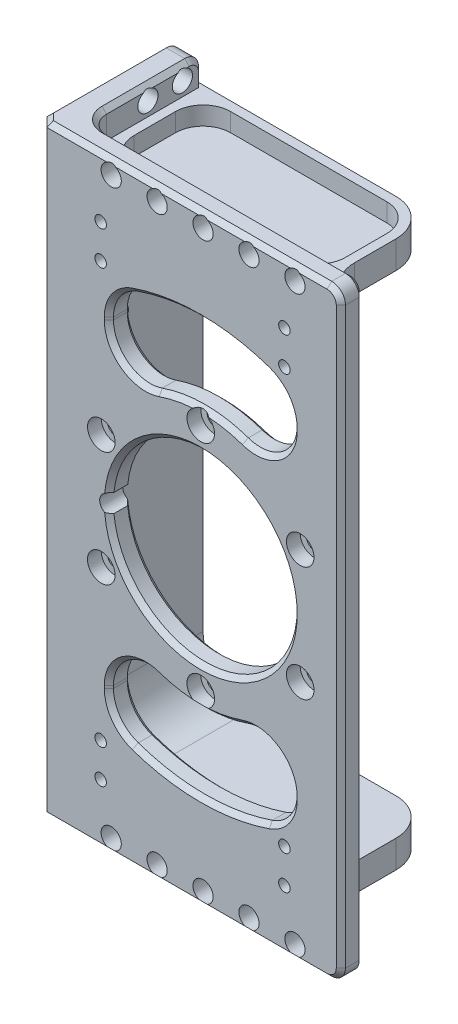
SolidWorks part; units mm, degrees
material "6061 合金"
ref_plane "前视基准面" through (0, 0, 0) normal (0, 0, 1) x (1, 0, 0)
ref_plane "上视基准面" through (0, 0, 0) normal (0, 1, 0) x (1, 0, 0)
ref_plane "右视基准面" through (0, 0, 0) normal (1, 0, 0) x (0, 0, -1)
sketch "草图1" plane through (0, 0, 0) normal (0, 0, 1) x (1, 0, 0)
  line L0 (-237.1759, 120) -> (-237.1759, 1) construction
  line L1 (-237.1759, 60.5) -> (-177.1759, 60.5) construction
  line L2 (812.8241, 60.5) -> (-387.1759, 60.5) construction
  line L3 (-165.4601, -5) -> (-232.1759, -5) construction
  line L4 (-237.1759, 126) -> (-177.1759, 126)
  line L5 (-237.1759, 126) -> (-237.1759, -5)
  line L6 (-237.1759, -5) -> (-177.1759, -5)
  line L7 (-177.1759, 126) -> (-177.1759, -5)
extrude "凸台-拉伸1" add sketch "草图1" along normal blind 5
sketch "草图2" plane through (-237.1759, 0, 0) normal (-1, 0, 0) x (0, 0, 1)
  line L0 (-235, 126) -> (-5, 126) construction
  line L1 (5, -5) -> (-25, -5)
  line L2 (5, -5) -> (5, 126)
  line L3 (5, 126) -> (-25, 126)
  line L4 (-25, -5) -> (-25, 126)
extrude "凸台-拉伸2" add sketch "草图2" along normal blind 6
sketch "草图3" plane through (0, 0, 5) normal (0, 0, 1) x (1, 0, 0)
  line L2 (-236.1759, 60.5) -> (-179.1759, 60.5) construction
  circle A2 centre (-207.6759, 60.5) radius 28.5 construction
  circle A3 centre (-207.6759, 60.5) radius 25 construction
  circle A4 centre (-207.6759, 60.5) radius 20
  dimension "D1" = 5
extrude "切除-拉伸1" cut sketch "草图3" against normal blind 10
sketch "草图4" plane through (0, 0, 5) normal (0, 0, 1) x (1, 0, 0)
  line L4 (-177.1759, 126) -> (-243.1759, 126)
  line L5 (-243.1759, 126) -> (-243.1759, -5)
  line L6 (-243.1759, -5) -> (-177.1759, -5)
  line L7 (-177.1759, -5) -> (-177.1759, 126)
  line L8 (-177.1759, 126) -> (-243.1759, 126)
  line L9 (-243.1759, 126) -> (-243.1759, -5)
  line L10 (-243.1759, -5) -> (-177.1759, -5)
  line L11 (-177.1759, -5) -> (-177.1759, 126)
  circle A0 centre (-207.6759, 60.5) radius 20 construction
  circle A1 centre (-207.6759, 60.5) radius 20
  dimension "D1" = 0
chamfer "倒角1" distance 2 angle 45 1 edges at (-243.1759, 60.5, 5)
fillet "圆角1" radius 3 4 edges at (-240.1759, 126, -25) (-177.1759, 126, 2.5) (-177.1759, -5, 2.5) (-240.1759, -5, -25)
sketch "草图5" plane through (0, 0, 5) normal (0, 0, 1) x (1, 0, 0)
  circle A0 centre (-207.6759, 60.5) radius 25 construction
  point P3 (-207.6759, 85.5)
  point P4 (-186.0252, 73)
  point P7 (-186.0252, 48)
  point P8 (-207.6759, 35.5)
  point P9 (-229.3265, 48)
  point P10 (-229.3265, 73)
  point P11 (-207.6759, 60.5)
  dimension "D1" = 6
sketch "草图13" plane through (0, 0, 5) normal (0, 0, 1) x (1, 0, 0)
  circle A0 centre (-207.6759, 85.5) radius 1.6
  circle A1 centre (-229.3265, 73) radius 1.6
  circle A2 centre (-186.0252, 73) radius 1.6
  circle A3 centre (-186.0252, 48) radius 1.6
  circle A4 centre (-207.6759, 35.5) radius 1.6
  circle A5 centre (-229.3265, 48) radius 1.6
extrude "切除-拉伸2" cut sketch "草图13" against normal blind 6
sketch "草图14" plane through (0, 0, 5) normal (0, 0, 1) x (1, 0, 0)
  circle A0 centre (-207.6759, 85.5) radius 3
  circle A1 centre (-186.0252, 73) radius 3
  circle A2 centre (-186.0252, 48) radius 3
  circle A3 centre (-207.6759, 35.5) radius 3
  circle A4 centre (-229.3265, 48) radius 3
  circle A5 centre (-229.3265, 73) radius 3
extrude "切除-拉伸3" cut sketch "草图14" against normal blind 3
chamfer "倒角4" distance 1 angle 45 12 edges at (-242.1759, -5, 4) (-210.6759, -5, 5) (-243.1759, -5, -9.5) (-178.0545, -4.1213, 5) (-243.1759, -4.1213, -24.1213) (-177.1759, 60.5, 5) (-243.1759, 60.5, -25) (-178.0545, 125.1213, 5) (-243.1759, 125.1213, -24.1213) (-210.6759, 126, 5) (-242.1759, 126, 4) (-243.1759, 126, -9.5)
sketch "草图15" plane through (0, 0, 0) normal (0, -1, 0) x (1, 0, 0)
  line L0 (-11.5, -120) -> (-5.5, -120) construction
  line L1 (-11.5, -191) -> (-11.5, -49) construction
  line L2 (-5.5, -108) -> (-5.5, -132) construction
  line L3 (-8.5, -100) -> (-8.5, -140) construction
  line L4 (-8.5, -80) -> (-8.5, -160) construction
  line L5 (-8.5, -60) -> (-8.5, -180) construction
  point P9 (-8.5, -120)
  point P13 (-8.5, -120)
  point P16 (-8.5, -120)
sketch "草图16" plane through (0, 0, 0) normal (0, 0, -1) x (-1, 0, 0)
  line L5 (237.1759, 126) -> (237.1759, 120) construction
  line L6 (237.1759, 123) -> (237.1759, -2) construction
  line L8 (237.1759, 120) -> (187.1759, 120)
  line L9 (237.1759, 120) -> (237.1759, 114)
  line L10 (237.1759, 114) -> (187.1759, 114)
  line L11 (187.1759, 120) -> (187.1759, 114)
extrude "凸台-拉伸4" add sketch "草图16" along normal up to surface (25 mm away) up to face at (-239.6759, 60.5, -25)
ref_plane "基准面1" through (0, 60.5, 0) normal (0, -1, 0) x (-1, 0, 0)
mirror "镜向1" about plane through (0, 60.5, 0) normal (0, -1, 0) of "凸台-拉伸4"
fillet "圆角3" radius 4 2 edges at (-237.1759, -2, 0) (-237.1759, 123, 0)
fillet "圆角4" radius 10 2 edges at (-237.1759, 114, -12.5) (-237.1759, 7, -12.5)
fillet "圆角5" radius 8 4 edges at (-187.1759, 117, 0) (-187.1759, 117, -25) (-187.1759, 4, 0) (-187.1759, 4, -25)
sketch "草图17" plane through (0, 120, 0) normal (0, 1, 0) x (1, 0, 0)
  line L4 (-235.1759, 4) -> (-235.1759, 2)
  line L5 (-235.1759, 2) -> (-233.1759, 2)
  line L8 (-189.1759, 8) -> (-189.1759, 17)
  line L9 (-195.1759, 23) -> (-235.1759, 23)
  line L10 (-235.1759, 23) -> (-235.1759, 4)
  line L11 (-233.1759, 2) -> (-187.1759, 2)
  line L12 (-189.1759, 8) -> (-189.1759, 17)
  line L13 (-195.1759, 23) -> (-235.1759, 23)
  line L14 (-235.1759, 23) -> (-235.1759, 4)
  line L15 (-233.1759, 2) -> (-187.1759, 2)
  arc A6 (-189.1759, 17) -> (-195.1759, 23) centre (-195.1759, 17) ccw
  arc A7 (-235.1759, 4) -> (-233.1759, 2) centre (-233.1759, 4) ccw
  arc A8 (-189.1759, 8) -> (-187.1759, 2) centre (-179.1759, 8) ccw
  arc A9 (-189.1759, 17) -> (-195.1759, 23) centre (-195.1759, 17) ccw
  arc A11 (-189.1759, 8) -> (-187.1759, 2) centre (-179.1759, 8) ccw
  dimension "D1" = 2
extrude "切除-拉伸4" cut sketch "草图17" against normal blind 4
mirror "镜向2" about plane through (0, 60.5, 0) normal (0, -1, 0) of "切除-拉伸4"
fillet "圆角6" radius 6 6 edges at (-187.1759, 118, -2) (-235.1759, 118, -23) (-235.1759, 118, -2) (-235.1759, 3, -23) (-187.1759, 3, -2) (-235.1759, 3, -2)
sketch "草图19" plane through (0, 0, 5) normal (0, 0, 1) x (1, 0, 0)
  line L0 (-243.1759, -5) -> (-237.1759, -5) construction
  line L1 (-243.1759, -5) -> (-177.1759, -5) construction
  line L2 (-237.1759, -5) -> (-177.1759, -5) construction
  line L3 (-207.1759, -5) -> (-207.1759, 1) construction
  line L4 (-217.1759, -2) -> (-197.1759, -2)
  line L5 (-227.1759, -2) -> (-187.1759, -2)
  circle A0 centre (-227.1759, -2) radius 2.2
  circle A1 centre (-217.1759, -2) radius 2.2
  circle A2 centre (-207.1759, -2) radius 2.2
  circle A3 centre (-197.1759, -2) radius 2.2
  circle A4 centre (-187.1759, -2) radius 2.2
  point P13 (-207.1759, -2)
  point P15 (-207.1759, -2)
  line M14 (-241.1759, -4) -> (-180.1759, -4)
extrude "切除-拉伸5" cut sketch "草图19" against normal blind 18 contours A0 M14 | L4 A1 L5 | L4 A2 | L5 A3 L4 | A4 M14 | L4 A3 L5 M14 | L4 A2 M14 | L5 A1 L4 M14 | A4 M14 | A3 M14 | A2 M14 | A1 M14 | A0 M14 region at (-217.1759, -1.0663, 5) region at (-217.1759, -2.8953, 5) region at (-207.1759, -1.0663, 5) region at (-207.1759, -2.8953, 5) region at (-217.1759, -4.0803, 5) region at (-227.1759, -1.9657, 5) region at (-207.1759, -4.0803, 5) region at (-227.1759, -4.0803, 5) region at (-197.1759, -1.0663, 5) region at (-197.1759, -2.8953, 5) region at (-197.1759, -4.0803, 5) region at (-187.1759, -1.9657, 5) region at (-187.1759, -4.0803, 5)
mirror "镜向3" about plane through (0, 60.5, 0) normal (0, -1, 0) of "切除-拉伸5"
sketch "草图20" plane through (-243.1759, 0, 0) normal (-1, 0, 0) x (0, 0, 1)
  line L0 (5, -5) -> (-1, -5) construction
  line L1 (5, -5) -> (5, 126) construction
  line L2 (4, -5) -> (2.5858, -5) construction
  line L3 (-1, -5) -> (-25, -5) construction
  line L4 (-5, -5) -> (-235, -5) construction
  line L5 (-13, -5) -> (-13, 1) construction
  line L6 (-20.5, -2) -> (-5.5, -2) construction
  circle A0 centre (-20.5, -2) radius 2.2
  circle A1 centre (-13, -2) radius 2.2
  point P15 (-13, -2)
extrude "切除-拉伸6" cut sketch "草图20" against normal blind 18
mirror "镜向4" about plane through (0, 60.5, 0) normal (0, -1, 0) of "切除-拉伸6"
sketch "草图21" plane through (0, 0, 5) normal (0, 0, 1) x (1, 0, 0)
  line L0 (-207.6759, 60.5) -> (-209.4659, 60.5)
  line L1 (-14.3, 60.5) -> (14.3, 60.5) construction
  line L2 (-209.4659, 60.5) -> (-209.4659, 64.19)
  line L4 (-229.4659, 113.065) -> (-189.4659, 113.065)
  line L5 (-229.4659, 113.065) -> (-229.4659, 15.315)
  line L6 (-229.4659, 15.315) -> (-189.4659, 15.315)
  line L7 (-189.4659, 113.065) -> (-189.4659, 15.315)
  line L8 (-229.4659, 113.065) -> (-189.4659, 15.315) construction
  line L9 (-229.4659, 15.315) -> (-189.4659, 113.065) construction
hole_wizard "M3 螺纹孔1" positions "草图22" profile "草图23" tap size "M3" standard "GB"
sketch "草图22" plane through (0, 0, 5) normal (0, 0, 1) x (1, 0, 0)
  point P0 (-229.4659, 113.065)
  point P3 (-189.4659, 113.065)
  point P6 (-189.4659, 15.315)
  point P9 (-229.4659, 15.315)
sketch "草图23" plane through (-229.4659, 113.065, 5) normal (1, 0, 0) x (0, -1, 0)
  line L0 (0, 0) -> (0, 8.2511)
  line L1 (0, 8.2511) -> (1.25, 7.5)
  line L2 (1.25, 7.5) -> (1.25, 0)
  line L5 (1.25, 0) -> (0, 0)
  line L10 (0, 8.2511) -> (-1.25, 7.5) construction
  line L11 (0, -6.35) -> (0, 107.95) construction
  dimension "螺纹孔钻头直径" = 2.5
  dimension "螺纹孔钻头深度" = 7.5
  dimension "导头角度" = 118
cosmetic thread "孔螺蚊线1" parameters "D1"=6, "D2"=3
cosmetic thread "孔螺蚊线2" parameters "D1"=6, "D2"=3
cosmetic thread "孔螺蚊线3" parameters "D1"=6, "D2"=3
cosmetic thread "孔螺蚊线4" parameters "D1"=6, "D2"=3
mirror "镜向5" about plane through (0, 60.5, 0) normal (0, -1, 0) of "M3 螺纹孔1"
cosmetic thread "孔螺蚊线5" parameters "D1"=6, "D2"=3
cosmetic thread "孔螺蚊线6" parameters "D1"=6, "D2"=3
cosmetic thread "孔螺蚊线7" parameters "D1"=6, "D2"=3
cosmetic thread "孔螺蚊线8" parameters "D1"=6, "D2"=3
sketch "草图24" plane through (-243.1759, 0, 0) normal (-1, 0, 0) x (0, 0, 1)
  line L0 (5, 60.5) -> (-7.12, 60.5)
  line L3 (-14.3, 60.5) -> (14.3, 60.5) construction
  line L4 (-7.12, 60.5) -> (-7.12, 35.2)
  line L5 (-7.12, 60.5) -> (-7.12, 85.8)
hole_wizard "M4 螺纹孔1" positions "草图25" profile "草图26" tap size "M4" standard "GB"
sketch "草图25" plane through (-243.1759, 0, 0) normal (-1, 0, 0) x (0, 0, 1)
  point P0 (-7.12, 85.8)
  point P3 (-7.12, 35.2)
sketch "草图26" plane through (-243.1759, 85.8, -7.12) normal (0, 1, 0) x (0, 0, 1)
  line L0 (0, 0) -> (0, 11.0914)
  line L1 (0, 11.0914) -> (1.65, 10.1)
  line L2 (1.65, 10.1) -> (1.65, 0)
  line L5 (1.65, 0) -> (0, 0)
  line L10 (0, 11.0914) -> (-1.65, 10.1) construction
  line L11 (0, -6.35) -> (0, 107.95) construction
  dimension "螺纹孔钻头直径" = 3.3
  dimension "螺纹孔钻头深度" = 10.1
  dimension "导头角度" = 118
cosmetic thread "孔螺蚊线9" parameters "D1"=8, "D2"=4
cosmetic thread "孔螺蚊线10" parameters "D1"=8, "D2"=4
sketch "草图27" plane through (0, 0, 0) normal (0, 0, -1) x (-1, 0, 0)
  line L0 (207.6759, 105.5) -> (207.6759, 89) construction
  line L1 (187.6759, 100.8113) -> (187.6759, 80.8039)
  line L2 (227.6759, 100.8113) -> (227.6759, 80.8039)
  line L3 (227.6759, 60.5) -> (227.6759, -966.5522) construction
  line L4 (207.6759, 60.5) -> (207.6759, -966.5522) construction
  line L5 (187.6759, 60.5) -> (187.6759, -966.5522) construction
  line L6 (187.6759, 40.1961) -> (187.6759, 20.1887)
  line L7 (207.6759, 32) -> (207.6759, 15.5) construction
  line L8 (227.6759, 40.1961) -> (227.6759, 20.1887)
  arc A0 (187.6759, 40.1961) -> (227.6759, 40.1961) centre (207.6759, 60.5) ccw
  arc A1 (187.6759, 20.1887) -> (227.6759, 20.1887) centre (207.6759, 60.5) ccw
  arc A2 (227.6759, 80.8039) -> (187.6759, 80.8039) centre (207.6759, 60.5) ccw
  arc A3 (227.6759, 100.8113) -> (187.6759, 100.8113) centre (207.6759, 60.5) ccw
  dimension "D1" = 20
  dimension "D2" = 20
extrude "切除-拉伸7" cut sketch "草图27" against normal blind 10
fillet "圆角7" radius 8 8 edges at (-187.6759, 20.1887, 2.5) (-227.6759, 40.1961, 2.5) (-227.6759, 20.1887, 2.5) (-187.6759, 40.1961, 2.5) (-187.6759, 80.8039, 2.5) (-227.6759, 100.8113, 2.5) (-227.6759, 80.8039, 2.5) (-187.6759, 100.8113, 2.5)
chamfer "倒角5" distance 1 angle 45 34 edges at (-187.6759, 60.5, 0) (-187.6759, 60.5, 5) (-207.6759, 105.5, 0) (-189.166, 100.1499, 0) (-226.1857, 100.1499, 0) (-187.6759, 95.2355, 0) (-227.6759, 95.2355, 0) (-191.0413, 88.4502, 0) (-224.3105, 88.4502, 0) (-207.6759, 89, 0) (-207.6759, 89, 5) (-191.0413, 88.4502, 5) (-224.3105, 88.4502, 5) (-187.6759, 95.2355, 5) (-227.6759, 95.2355, 5) (-189.166, 100.1499, 5) (-226.1857, 100.1499, 5) (-207.6759, 105.5, 5) (-207.6759, 32, 0) (-191.0413, 32.5498, 0) (-224.3105, 32.5498, 0) (-187.6759, 25.7645, 0) (-227.6759, 25.7645, 0) (-189.166, 20.8501, 0) (-226.1857, 20.8501, 0) (-207.6759, 15.5, 0) (-207.6759, 32, 5) (-224.3105, 32.5498, 5) (-191.0413, 32.5498, 5) (-227.6759, 25.7645, 5) (-187.6759, 25.7645, 5) (-226.1857, 20.8501, 5) (-189.166, 20.8501, 5) (-207.6759, 15.5, 5)
chamfer "倒角6" distance 1 angle 45 13 edges at (-237.1759, -0.5, -25) (-237.1759, 121.5, -25) (-237.1759, -4.1213, -24.1213) (-237.1759, 125.1213, -24.1213) (-237.1759, -5, -13) (-237.1759, 126, -13) (-236.0043, -5, -1.1716) (-236.0043, 126, -1.1716) (-206.6759, -5, 0) (-206.6759, 126, 0) (-178.0545, -4.1213, 0) (-178.0545, 125.1213, 0) (-177.1759, 60.5, 0)
sketch "草图29" plane through (0, 0, 5) normal (0, 0, 1) x (1, 0, 0)
  circle A0 centre (-227.6759, 60.5) radius 2
  dimension "D1" = 4
extrude "切除-拉伸8" cut sketch "草图29" against normal blind 10
sketch "草图30" plane through (0, 0, 0) normal (0, 0, -1) x (-1, 0, 0)
  circle A0 centre (214.1463, 36.3519) radius 1.5
  dimension "D1" = 3
extrude "切除-拉伸9" cut sketch "草图30" against normal blind 3
pattern_circular "阵列(圆周)1" count 6 over 360 about axis through (-207.6759, 60.5, -5) along (0, 0, 1) of "切除-拉伸9" reverse direction yes
